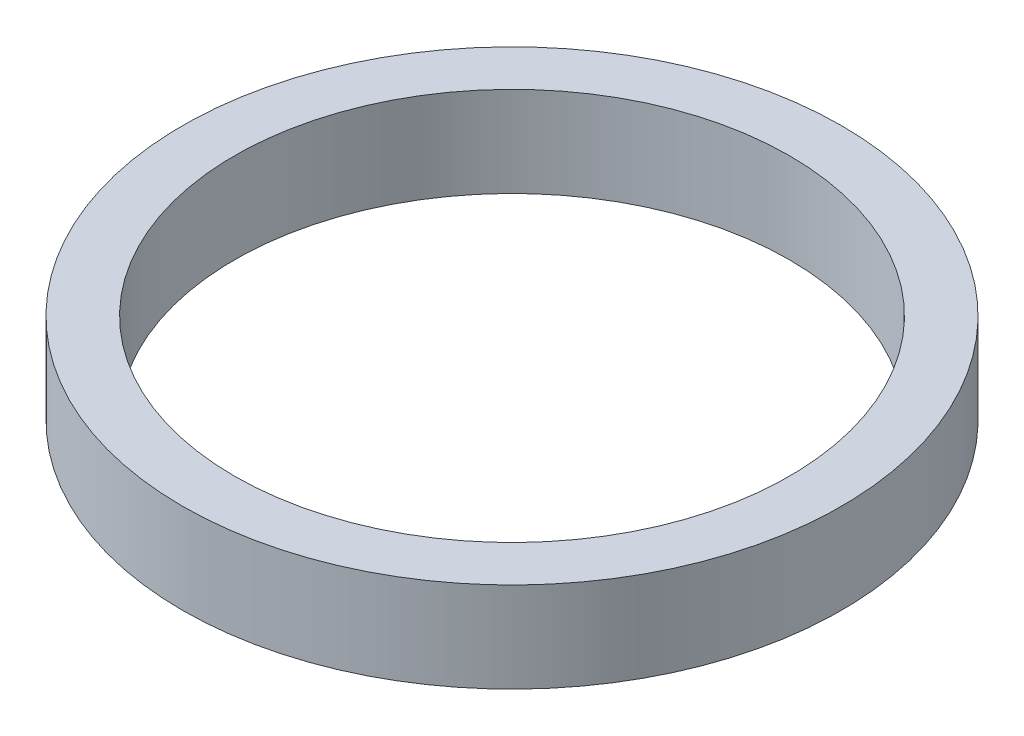
SolidWorks part; units mm, degrees
ref_plane "Front Plane" through (0, 0, 0) normal (0, 0, 1) x (1, 0, 0)
ref_plane "Top Plane" through (0, 0, 0) normal (0, 1, 0) x (1, 0, 0)
ref_plane "Right Plane" through (0, 0, 0) normal (1, 0, 0) x (0, 0, -1)
sketch "Sketch1" plane through (0, 0, 0) normal (0, 1, 0) x (1, 0, 0)
  circle A0 centre (0, 0) radius 47.5
  dimension "FLANGE_OD" = 95
extrude "Boss-Extrude1" add sketch "Sketch1" along normal blind 13
sketch "Sketch2" plane through (0, 0, 0) normal (0, 1, 0) x (1, 0, 0)
  circle A0 centre (0, 0) radius 40
  dimension "BORE_D" = 80
extrude "Cut-Extrude1" cut sketch "Sketch2" along normal through all
sketch "Sketch3" plane through (0, 13, 0) normal (0, 1, 0) x (1, 0, 0)
  circle A0 centre (0, 0) radius 21.8392 construction
  circle A1 centre (-21.8392, 0) radius 1.5
  dimension "BOLT_D" = 3
  dimension "BOLT_PCD" = 43.6784
extrude "Cut-Extrude2" cut sketch "Sketch3" against normal blind 9.8227 rebuild error yes
pattern_circular "CirPattern1" count 3 over 360 rebuild error yes
